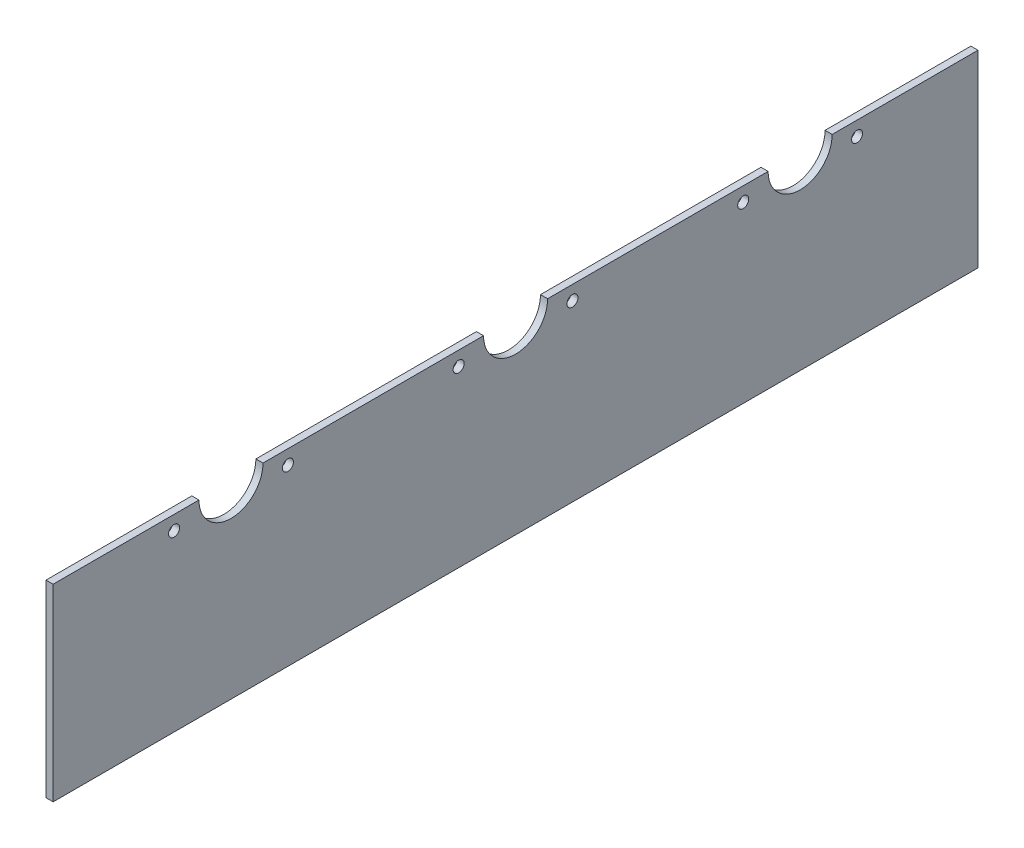
SolidWorks part; units mm, degrees
ref_plane "Front Plane" through (0, 0, 0) normal (0, 0, 1) x (1, 0, 0)
ref_plane "Top Plane" through (0, 0, 0) normal (0, 1, 0) x (1, 0, 0)
ref_plane "Right Plane" through (0, 0, 0) normal (1, 0, 0) x (0, 0, -1)
sketch "Sketch1" plane through (0, 0, 0) normal (1, 0, 0) x (0, 0, -1)
  line L0 (206.375, 0) -> (-206.375, 0)
  line L1 (-206.375, 0) -> (-206.375, 84.1375)
  line L2 (-206.375, 84.1375) -> (-141.2875, 84.1375)
  line L3 (-112.7125, 84.1375) -> (-14.2875, 84.1375)
  line L4 (14.2875, 84.1375) -> (112.7125, 84.1375)
  line L5 (141.2875, 84.1375) -> (206.375, 84.1375)
  line L6 (206.375, 84.1375) -> (206.375, 0)
  line L7 (-206.375, 25.4) -> (206.375, 25.4) construction
  arc A6 (-141.2875, 84.1375) -> (-112.7125, 84.1375) centre (-127, 84.1375) ccw
  arc A7 (-14.2875, 84.1375) -> (14.2875, 84.1375) centre (0, 84.1375) ccw
  arc A8 (112.7125, 84.1375) -> (141.2875, 84.1375) centre (127, 84.1375) ccw
  point P3 (112.7125, 77.7875)
  point P4 (0, 0)
  point P15 (141.2875, 77.7875)
  point P17 (14.2875, 77.7875)
  point P23 (-112.7125, 77.7875)
  point P24 (-14.2875, 77.7875)
  point P25 (-141.4675, 77.7875)
  dimension "D1" = 25.4
  dimension "D5" = 28.575
  dimension "D6" = 44.45
  dimension "D2" = 412.75
  dimension "D4" = 127
extrude "Boss-Extrude1" add sketch "Sketch1" along normal blind 3.175
hole_wizard "#10 (0.1935) Diameter Hole1" positions "Sketch2" profile "Sketch3" hole size "#10" standard "ANSI Inch" end condition through all
sketch "Sketch2" plane through (3.175, 0, 0) normal (1, 0, 0) x (0, 0, -1)
  line L0 (-152.4, 77.7875) -> (-101.6, 77.7875) construction
  line L2 (-25.4, 77.7875) -> (25.4, 77.7875) construction
  line L4 (101.6, 77.7875) -> (152.4, 77.7875) construction
  line L6 (-141.2875, 84.1375) -> (-206.375, 84.1375) construction
  line L7 (-127, 77.7875) -> (-127, 84.1375) construction
  line L9 (0, 84.1375) -> (0, 77.7875) construction
  line L11 (127, 84.1375) -> (127, 77.7875) construction
  point P0 (-152.4, 77.7875)
  point P2 (-101.6, 77.7875)
  point P4 (-25.4, 77.7875)
  point P6 (25.4, 77.7875)
  point P8 (101.6, 77.7875)
  point P10 (152.4, 77.7875)
  dimension "D1" = 50.8
  dimension "D2" = 6.35
sketch "Sketch3" plane through (3.175, 77.7875, 152.4) normal (0, 1, 0) x (0, 0, -1)
  line L0 (0, 0) -> (0, 3.175)
  line L1 (0, 3.175) -> (2.4574, 3.175)
  line L2 (2.4574, 3.175) -> (2.4574, 0)
  line L5 (2.4574, 0) -> (0, 0)
  line L11 (0, -6.35) -> (0, 107.95) construction
  dimension "Thru Hole Dia." = 4.9149
  dimension "Thru Hole Depth" = 3.175
